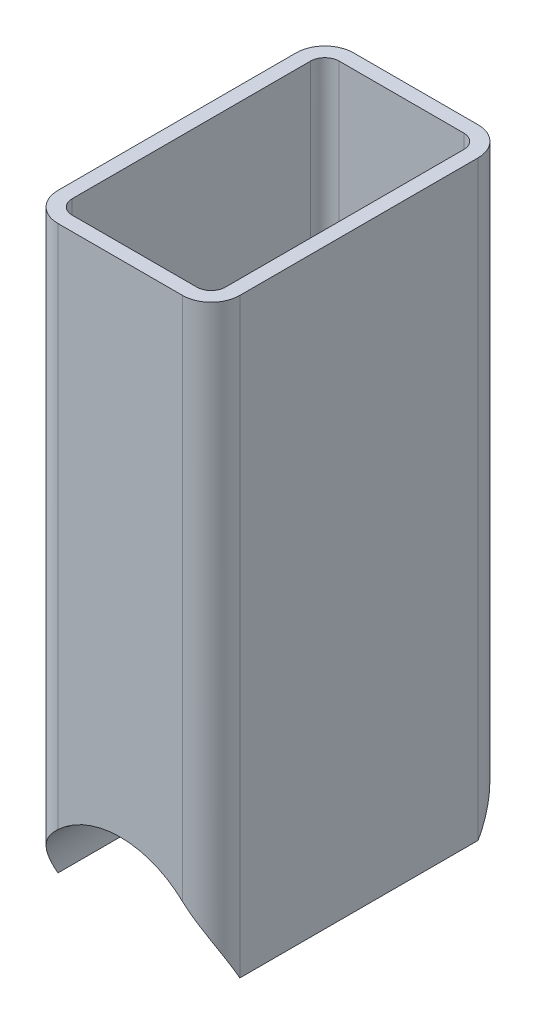
SolidWorks part; units mm, degrees
material "1.0037 (S235JR)"
ref_plane "E_Rechts" through (0, 0, 0) normal (0, 0, 1) x (1, 0, 0)
ref_plane "E_Vorne" through (0, 0, 0) normal (0, 1, 0) x (1, 0, 0)
ref_plane "E_Oben" through (0, 0, 0) normal (1, 0, 0) x (0, 0, -1)
sketch "Skizze1" plane through (0, 0, 0) normal (0, 1, 0) x (1, 0, 0)
  line L0 (-27.4, -58.7) -> (27.4, -58.7)
  line L1 (-33.7, -52.4) -> (-33.7, 52.4)
  line L2 (27.4, 58.7) -> (-27.4, 58.7)
  line L3 (33.7, 52.4) -> (33.7, -52.4)
  line L4 (-27.4, -65) -> (27.4, -65)
  line L5 (-40, -52.4) -> (-40, 52.4)
  line L6 (27.4, 65) -> (-27.4, 65)
  line L7 (40, 52.4) -> (40, -52.4)
  line L8 (-55, 0) -> (55, 0) construction
  line L9 (0, -55) -> (0, 55) construction
  arc A0 (40, 52.4) -> (27.4, 65) centre (27.4, 52.4) ccw
  arc A1 (27.4, -65) -> (40, -52.4) centre (27.4, -52.4) ccw
  arc A2 (-40, -52.4) -> (-27.4, -65) centre (-27.4, -52.4) ccw
  arc A3 (-27.4, 65) -> (-40, 52.4) centre (-27.4, 52.4) ccw
  arc A4 (-27.4, 58.7) -> (-33.7, 52.4) centre (-27.4, 52.4) ccw
  arc A5 (33.7, 52.4) -> (27.4, 58.7) centre (27.4, 52.4) ccw
  arc A6 (27.4, -58.7) -> (33.7, -52.4) centre (27.4, -52.4) ccw
  arc A7 (-33.7, -52.4) -> (-27.4, -58.7) centre (-27.4, -52.4) ccw
  dimension "D1" = 12.6
  dimension "D2" = 6.3
  dimension "D3" = 130
  dimension "D4" = 80
  dimension "D5" = 65
  dimension "D6" = 65
  dimension "D7" = 40
  dimension "D8" = 40
extrude "Aufsatz-Linear austragen1" add sketch "Skizze1" along normal blind 260
sketch "Skizze2" plane through (0, 0, 0) normal (0, 0, 1) x (1, 0, 0)
  circle A0 centre (0, 0) radius 40
extrude "Schnitt-Linear austragen1" cut sketch "Skizze2" against normal through all both and the other way through all
